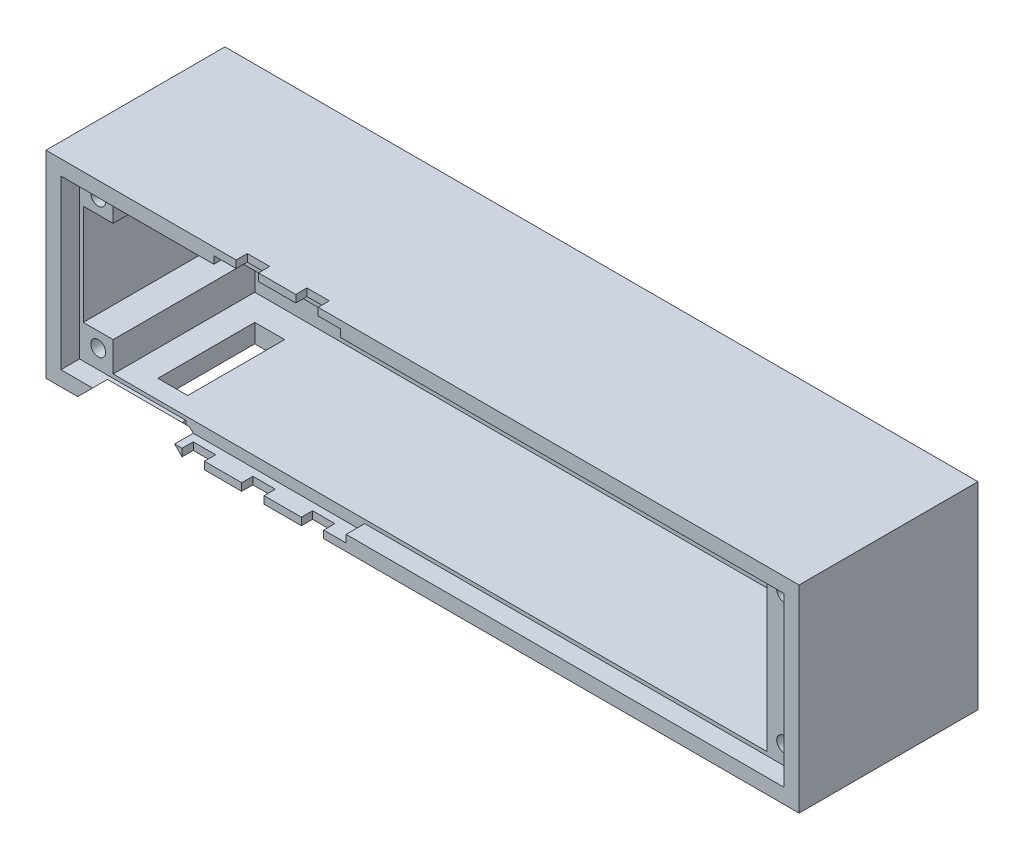
SolidWorks part; units mm, degrees
ref_plane "前视基准面" through (0, 0, 0) normal (0, 0, 1) x (1, 0, 0)
ref_plane "上视基准面" through (0, 0, 0) normal (0, 1, 0) x (1, 0, 0)
ref_plane "右视基准面" through (0, 0, 0) normal (1, 0, 0) x (0, 0, -1)
other "Configuration Table"
sketch "草图1" plane through (0, 0, 0) normal (0, 0, 1) x (1, 0, 0)
  line L1 (0, 0) -> (101, 0)
  line L2 (0, 0) -> (0, 26.5)
  line L3 (0, 26.5) -> (101, 26.5)
  line L4 (101, 0) -> (101, 26.5)
  dimension "D1" = 101
  dimension "D2" = 26.5
extrude "凸台-拉伸1" add sketch "草图1" along normal blind 2.5
sketch "草图2" plane through (0, 0, 2.5) normal (0, 0, 1) x (1, 0, 0)
  line L0 (98.5, 24) -> (2.5, 24)
  line L1 (2.5, 24) -> (2.5, 2.5)
  line L2 (2.5, 2.5) -> (98.5, 2.5)
  line L3 (98.5, 2.5) -> (98.5, 24)
  line L4 (0, 26.5) -> (0, 0)
  line L5 (0, 0) -> (101, 0)
  line L6 (101, 0) -> (101, 26.5)
  line L7 (101, 26.5) -> (0, 26.5)
  line L8 (0, 26.5) -> (0, 0)
  line L9 (0, 0) -> (101, 0)
  line L10 (101, 0) -> (101, 26.5)
  line L11 (101, 26.5) -> (0, 26.5)
  dimension "D1" = 0
  dimension "D2" = 2.5
extrude "凸台-拉伸2" add sketch "草图2" along normal blind 21.5
sketch "草图3" plane through (0, 0, 2.5) normal (0, 0, 1) x (1, 0, 0)
  line L1 (2.5, 24) -> (6.5, 24)
  line L2 (2.5, 24) -> (2.5, 20)
  line L4 (6.5, 24) -> (6.5, 20)
  line L5 (2.5, 2.5) -> (6.5, 2.5)
  line L6 (2.5, 2.5) -> (2.5, 6.5)
  line L8 (6.5, 2.5) -> (6.5, 6.5)
  line L9 (98.5, 24) -> (95.1958, 24)
  line L10 (98.5, 24) -> (98.5, 17.7456)
  line L12 (95.1958, 24) -> (95.1958, 20)
  line L13 (98.5, 2.5) -> (95.1958, 2.5)
  line L14 (98.5, 2.5) -> (98.5, 8.7544)
  line L16 (95.1958, 2.5) -> (95.1958, 6.5)
  line L21 (2.5, 20) -> (6.5, 20)
  line L23 (2.5, 6.5) -> (6.5, 6.5)
  line L26 (95.1958, 20) -> (95.1958, 6.5)
  line L28 (98.5, 17.7456) -> (98.5, 8.7544)
  dimension "D1" = 4
  dimension "D2" = 4
  dimension "D3" = 4
  dimension "D4" = 4
  dimension "D5" = 4
  dimension "D6" = 4
  dimension "D7" = 4
  dimension "D8" = 4
extrude "凸台-拉伸3" add sketch "草图3" along normal blind 19
sketch "草图5" plane through (0, 0, 21.5) normal (0, 0, 1) x (1, 0, 0)
  line L0 (2.5, 24) -> (6.5, 20) construction
  line L1 (6.5, 6.5) -> (2.5, 2.5) construction
  line L2 (98.5, 2.5) -> (98.5, 24) construction
  line L3 (98.5, 24) -> (95.1958, 24) construction
  line L10 (98.5, 2.5) -> (98.5, 24) construction
  circle A0 centre (4.5, 22) radius 1
  circle A1 centre (4.5, 4.5) radius 1
  circle A2 centre (96.5, 22) radius 1
  circle A3 centre (96.5, 4.5) radius 1
  dimension "D1" = 2
  dimension "D2" = 2
  dimension "D3" = 2
  dimension "D4" = 17.5
  dimension "D5" = 2
extrude "切除-拉伸1" cut sketch "草图5" against normal blind 12
sketch "草图6" plane through (0, 0, 0) normal (0, -1, 0) x (1, 0, 0)
  line L6 (0, 24) -> (0, 0) construction
  line L7 (10, 19) -> (55, 19)
  line L8 (10, 19) -> (10, 6)
  line L9 (10, 6) -> (55, 6)
  line L10 (55, 19) -> (55, 6)
  line L11 (0, 24) -> (101, 24) construction
  dimension "D1" = 13
  dimension "D2" = 45
  dimension "D3" = 10
  dimension "D4" = 5
extrude "切除-拉伸2" cut sketch "草图6" against normal blind 1.5
sketch "草图7" plane through (0, 1.5, 0) normal (0, -1, 0) x (1, 0, 0)
  line L0 (10, 6) -> (55, 6) construction
  line L1 (10, 19) -> (14, 19)
  line L2 (10, 19) -> (10, 6)
  line L3 (10, 6) -> (14, 6)
  line L4 (14, 19) -> (14, 6)
  dimension "D1" = 4
extrude "切除-拉伸3" cut sketch "草图7" against normal blind 1.5
sketch "草图8" plane through (0, 0, 24) normal (0, 0, 1) x (1, 0, 0)
  line L8 (99, 24.5) -> (2, 24.5)
  line L9 (2, 24.5) -> (2, 2)
  line L10 (2, 2) -> (99, 2)
  line L11 (99, 2) -> (99, 24.5)
  line L12 (99, 24.5) -> (2, 24.5)
  line L13 (2, 24.5) -> (2, 2)
  line L14 (2, 2) -> (99, 2)
  line L15 (99, 2) -> (99, 24.5)
  dimension "D1" = 2
extrude "切除-拉伸4" cut sketch "草图8" against normal up to surface (2.5 mm away) contours L12 L13 L14 L15 up to face at (5.5, 22, 21.5)
sketch "草图9" plane through (0, 0, 0) normal (0, -1, 0) x (1, 0, 0)
  line L0 (0, 24) -> (101, 24) construction
  line L1 (6.25, 24) -> (16.25, 24)
  line L2 (6.25, 24) -> (6.25, 22)
  line L3 (6.25, 22) -> (16.25, 22)
  line L4 (16.25, 24) -> (16.25, 22)
  line L5 (0, 24) -> (0, 0) construction
  line L7 (18.25, 24) -> (21.25, 24)
  line L8 (18.25, 24) -> (18.25, 22.5)
  line L9 (18.25, 22.5) -> (21.25, 22.5)
  line L10 (21.25, 24) -> (21.25, 22.5)
  line L11 (26.25, 24) -> (29.25, 24)
  line L12 (26.25, 24) -> (26.25, 22.5)
  line L13 (26.25, 22.5) -> (29.25, 22.5)
  line L14 (29.25, 24) -> (29.25, 22.5)
  line L15 (34.25, 24) -> (37.25, 24)
  line L16 (34.25, 24) -> (34.25, 22.5)
  line L17 (34.25, 22.5) -> (37.25, 22.5)
  line L18 (37.25, 24) -> (37.25, 22.5)
  dimension "D1" = 6.25
  dimension "D2" = 10
  dimension "D3" = 2
  dimension "D4" = 1.5
  dimension "D5" = 2
  dimension "D6" = 3
  dimension "D7" = 5
  dimension "D8" = 3
  dimension "D9" = 1.5
  dimension "D10" = 5
  dimension "D11" = 3
  dimension "D12" = 1.5
extrude "切除-拉伸5" cut sketch "草图9" against normal up to next
chamfer "倒角1" distance 2 angle 45 3 edges at (16.25, 0, 23) (11.25, 0, 22) (6.25, 0, 23)
sketch "草图11" plane through (0, 26.5, 0) normal (0, 1, 0) x (1, 0, 0)
  line L6 (101, -24) -> (0, -24) construction
  line L7 (28.5, -24) -> (25.5, -24)
  line L8 (28.5, -24) -> (28.5, -22.5)
  line L9 (28.5, -22.5) -> (25.5, -22.5)
  line L10 (25.5, -24) -> (25.5, -22.5)
  line L11 (0, -24) -> (0, 0) construction
  line L13 (33.5, -24) -> (36.5, -24)
  line L14 (33.5, -24) -> (33.5, -22.5)
  line L15 (33.5, -22.5) -> (36.5, -22.5)
  line L16 (36.5, -24) -> (36.5, -22.5)
  dimension "D1" = 25.5
  dimension "D2" = 1.5
  dimension "D3" = 3
  dimension "D4" = 3
  dimension "D5" = 5
  dimension "D6" = 1.5
extrude "切除-拉伸6" cut sketch "草图11" against normal up to next
sketch "草图12" plane through (0, 0, 0) normal (0, 0, -1) x (-1, 0, 0)
  line L1 (-6, 18.5) -> (-3, 18.5)
  line L2 (-6, 18.5) -> (-6, 15.5)
  line L3 (-6, 15.5) -> (-3, 15.5)
  line L4 (-3, 18.5) -> (-3, 15.5)
  line L6 (0, 26.5) -> (0, 0) construction
  line L7 (-101, 26.5) -> (0, 26.5) construction
  dimension "D1" = 3
  dimension "D2" = 8
  dimension "D3" = 3
  dimension "D4" = 3
extrude "切除-拉伸7" cut sketch "草图12" against normal up to next
sketch "草图14" plane through (0, 0, 2.5) normal (0, 0, 1) x (1, 0, 0)
  line L0 (6, 15.5) -> (6, 18.5) construction
  line L1 (2.5, 20) -> (6.5, 20)
  line L2 (2.5, 20) -> (2.5, 14.5)
  line L3 (2.5, 14.5) -> (6.5, 14.5)
  line L4 (6.5, 20) -> (6.5, 14.5)
  line L5 (3, 15.5) -> (6, 15.5) construction
  line L6 (3, 18.5) -> (3, 15.5) construction
  line L7 (6, 18.5) -> (3, 18.5) construction
  line L8 (6, 15.5) -> (6, 18.5)
  line L9 (3, 15.5) -> (6, 15.5)
  line L10 (3, 18.5) -> (3, 15.5)
  line L11 (6, 18.5) -> (3, 18.5)
  line L12 (6.5, 20) -> (6.5, 24) construction
  line M6 (3, 18.5) -> (6, 18.5)
  line M7 (6, 18.5) -> (6, 15.5)
  line M8 (6, 15.5) -> (3, 15.5)
  line M9 (3, 15.5) -> (3, 18.5)
  dimension "D1" = 0
  dimension "D2" = 1
extrude "凸台-拉伸4" add sketch "草图14" along normal blind 5 contours M6 M9 M8 M7 | L2 L1 L4 L3 region at (4.5, 17, 2.5)
sketch "草图13" plane through (0, 0, 0) normal (-1, 0, 0) x (0, 0, 1)
  line L0 (24, 26.5) -> (0, 26.5) construction
  line L1 (3, 18.5) -> (6, 18.5)
  line L2 (3, 18.5) -> (3, 15.5)
  line L3 (3, 15.5) -> (6, 15.5)
  line L4 (6, 18.5) -> (6, 15.5)
  line L5 (0, 26.5) -> (0, 0) construction
  dimension "D1" = 8
  dimension "D2" = 3
  dimension "D3" = 3
  dimension "D4" = 3
extrude "切除-拉伸8" cut sketch "草图13" against normal up to next
sketch "草图15" plane through (0, 0, 7.5) normal (0, 0, 1) x (1, 0, 0)
  line L4 (2.5, 14.5) -> (6.5, 14.5)
  line L5 (6.5, 14.5) -> (6.5, 20)
  line L6 (6.5, 20) -> (2.5, 20)
  line L7 (2.5, 20) -> (2.5, 14.5)
  line L8 (2.5, 14.5) -> (6.5, 14.5)
  line L9 (6.5, 14.5) -> (6.5, 20)
  line L10 (6.5, 20) -> (2.5, 20)
  line L11 (2.5, 20) -> (2.5, 14.5)
  dimension "D1" = 0
extrude "凸台-拉伸5" add sketch "草图15" against normal up to surface (1.5 mm away) up to face at (1.5, 17, 6)
sketch "草图16" plane through (95.1958, 0, 0) normal (-1, 0, 0) x (0, 0, 1)
  line L4 (2.5, 24) -> (2.5, 2.5)
  line L5 (2.5, 2.5) -> (21.5, 2.5)
  line L6 (21.5, 2.5) -> (21.5, 24)
  line L7 (21.5, 24) -> (2.5, 24)
  line L8 (2.5, 24) -> (2.5, 2.5)
  line L9 (2.5, 2.5) -> (21.5, 2.5)
  line L10 (21.5, 2.5) -> (21.5, 24)
  line L11 (21.5, 24) -> (2.5, 24)
  dimension "D1" = 0
extrude "凸台-拉伸6" add sketch "草图16" along normal blind 1
sketch "草图18" plane through (0, 0, 24) normal (0, 0, 1) x (1, 0, 0)
  line L0 (2, 24.5) -> (99, 24.5) construction
  line L1 (22.5, 24.5) -> (39.5, 24.5)
  line L2 (22.5, 24.5) -> (22.5, 25.5)
  line L3 (22.5, 25.5) -> (39.5, 25.5)
  line L4 (39.5, 24.5) -> (39.5, 25.5)
  line L5 (36.5, 24.5) -> (36.5, 26.5) construction
  line L6 (25.5, 24.5) -> (25.5, 26.5) construction
  line L7 (16.25, 2) -> (18.25, 0) construction
  line L8 (16.25, 2) -> (40.25, 2)
  line L9 (16.25, 2) -> (16.25, 1)
  line L10 (16.25, 1) -> (40.25, 1)
  line L11 (40.25, 2) -> (40.25, 1)
  line L12 (16.25, 2) -> (18.25, 0) construction
  line L13 (37.25, 2) -> (37.25, 0) construction
  point P6 (39.5, 25)
  point P9 (22.5, 25)
  dimension "D1" = 1
  dimension "D2" = 3
  dimension "D3" = 3
  dimension "D4" = 1
  dimension "D5" = 3
extrude "切除-拉伸9" cut sketch "草图18" against normal up to surface (2.5 mm away) up to face at (27.424, 13.25, 21.5)
